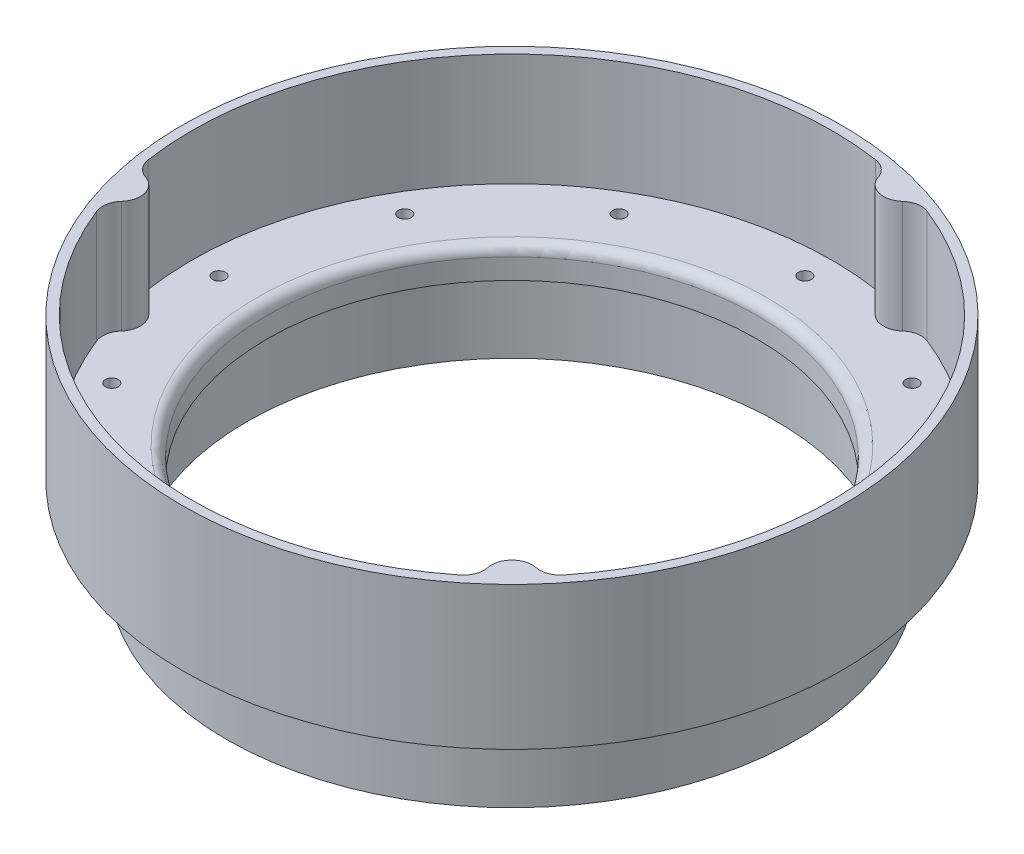
SolidWorks part; units mm, degrees
material "6061-T6 (SS)"
ref_plane "Front Plane" through (0, 0, 0) normal (0, 0, 1) x (1, 0, 0)
ref_plane "Top Plane" through (0, 0, 0) normal (0, 1, 0) x (1, 0, 0)
ref_plane "Right Plane" through (0, 0, 0) normal (1, 0, 0) x (0, 0, -1)
ref_axis "Axis1" through (0, 55, 0) along (0, -1, 0)
sketch "Cross Section" plane through (0, 0, 0) normal (0, 0, 1) x (1, 0, 0)
  line L0 (-38.1, 0) -> (-38.1, -3.175)
  line L1 (-38.1, -3.175) -> (-41.2242, -3.175)
  line L2 (-41.2242, -3.175) -> (-41.2242, -15.875)
  line L4 (0, -15.875) -> (-38.1, -15.875) construction
  line L5 (-44.3992, -15.875) -> (-44.3992, -3.175)
  line L6 (-44.3992, -3.175) -> (-51.2572, -3.175)
  line L7 (-51.2572, -3.175) -> (-51.2572, 19.05)
  line L8 (-51.2572, 19.05) -> (-49.784, 19.05)
  line L9 (-49.784, 19.05) -> (-49.784, 1.5875)
  line L11 (-38.1, 0) -> (0, 0) construction
  line L13 (-44.3992, -15.875) -> (-41.2242, -15.875)
  line L14 (-49.784, 1.5875) -> (-49.784, 3.175) construction
  line L15 (-39.6875, 1.5875) -> (-49.784, 1.5875)
  arc A0 (-39.6875, 1.5875) -> (-38.1, 0) centre (-39.6875, 0) cw
  dimension "D2" = 1.5875
  dimension "D1" = 3.1242
  dimension "D3" = 3.175
  dimension "D5" = 6.858
  dimension "D6" = 22.225
  dimension "D9" = 3.175
  dimension "D4" = 1.5875
  dimension "D7" = 38.1
revolve "Main" add sketch "Cross Section" angle 360 about axis through (0, 55, 0) along (0, -1, 0)
sketch "Hole Location" plane through (0, 0, 0) normal (0, 1, 0) x (1, 0, 0)
  line L0 (0, 0) -> (-45.5549, 0) construction
  circle A0 centre (0, 0) radius 45.5549 construction
  dimension "D1" = 91.1098
hole_wizard "#3-48 Tapped Hole1" positions "Sketch1" profile "Sketch2" tap size "#3-48" standard "ANSI Inch" end condition through all
sketch "Sketch1" plane through (0, 1.5875, 0) normal (0, 1, 0) x (1, 0, 0)
  point P0 (-45.5549, 0)
sketch "Sketch2" plane through (-45.5549, 1.5875, 0) normal (1, 0, 0) x (0, 0, 1)
  line L0 (0, 0) -> (0, 17.4625)
  line L1 (0, 17.4625) -> (0.9969, 17.4625)
  line L2 (0.9969, 17.4625) -> (0.9969, 0)
  line L5 (0.9969, 0) -> (0, 0)
  line L11 (0, -6.35) -> (0, 107.95) construction
  dimension "Thru Tap Drill Dia." = 1.9939
  dimension "Thru Tap Drill Depth" = 17.4625
cosmetic thread "Hole Thread1" parameters "D2"=2.5146
pattern_circular "CirPattern1" count 12 over 360 of "#3-48 Tapped Hole1"
sketch "Sketch3" plane through (0, 1.5875, 0) normal (0, 1, 0) x (1, 0, 0)
  line L0 (0, 0) -> (-48.0877, -12.885) construction
  line L1 (0, 0) -> (-45.5549, 0) construction
  circle A0 centre (0, 0) radius 49.784 construction
  circle A1 centre (0, 0) radius 49.784 construction
  circle A2 centre (0, 0) radius 49.784 construction
  arc A3 (-47.095, -9.8692) -> (-45.7201, -15.0005) centre (-48.0877, -12.885) cw
  arc A4 (-45.7201, -15.0005) -> (-46.3057, -18.282) centre (-43.3525, -17.116) ccw
  arc A5 (-47.095, -9.8692) -> (-49.2429, -7.3202) centre (-46.1024, -6.8534) cw
  arc A6 (-46.3057, -18.282) -> (-49.2429, -7.3202) centre (0, 0) cw
  arc A7 (15.0005, 45.7201) -> (9.8692, 47.095) centre (12.885, 48.0877) cw
  arc A8 (9.8692, 47.095) -> (7.3202, 49.2429) centre (6.8534, 46.1024) ccw
  arc A9 (7.3202, 49.2429) -> (18.282, 46.3057) centre (0, 0) cw
  arc A10 (15.0005, 45.7201) -> (18.282, 46.3057) centre (17.116, 43.3525) cw
  arc A11 (32.0945, -35.8509) -> (35.8509, -32.0945) centre (35.2026, -35.2026) cw
  arc A12 (35.8509, -32.0945) -> (38.9855, -30.9609) centre (36.4992, -28.9864) ccw
  arc A13 (38.9855, -30.9609) -> (30.9609, -38.9855) centre (0, 0) cw
  arc A14 (32.0945, -35.8509) -> (30.9609, -38.9855) centre (28.9864, -36.4992) cw
  point P36 (0, 0)
  dimension "D1" = 15
  dimension "D2" = 3.175
  dimension "D3" = 3.175
  dimension "D4" = 3
extrude "Boss-Extrude1" add sketch "Sketch3" along normal up to surface (17.4625 mm away) up to face at (0, 19.05, 51.2572)
equation "\"D1@Hole Location\"=\"TANK DIAMETER@Cryo Tank.Assembly\"+\"GASKET SEAT THICKNESS@Cryo Tank.Assembly\"+\"LINER THICKNESS@Cryo Tank.Assembly\"+\"SHRINK FIT DELTA@Cryo Tank.Assembly\""
equation "\"D1@Cross Section\"=\"LINER THICKNESS@Cryo Tank.Assembly\"-0.002"
equation "\"D3@Cross Section\"=\"ALUMINUM LAP THICKNESS@Cryo Tank.Assembly\""
equation "\"D5@Cross Section\"=2*\"CF THICKNESS@Cryo Tank.Assembly\"+\"NOMEX THICKNESS@Cryo Tank.Assembly\""
equation "\"D7@Cross Section\"=\"TANK DIAMETER@Cryo Tank.Assembly\"/2"
